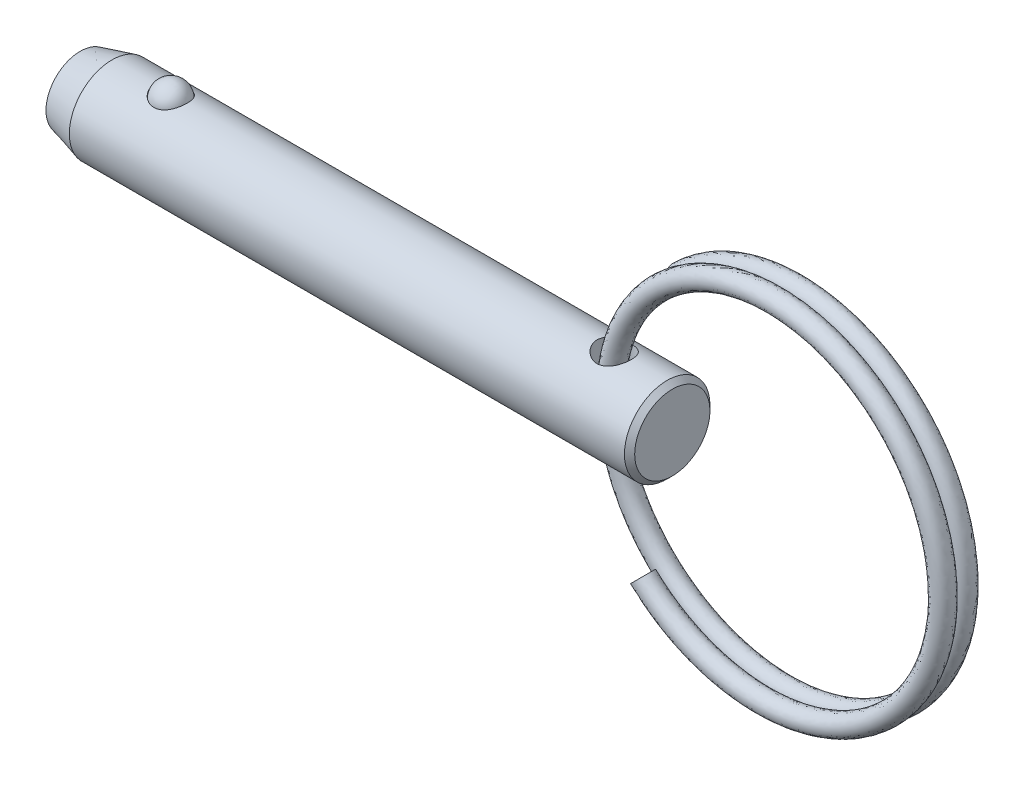
SolidWorks part; units mm, degrees
material "Plain Carbon Steel"
ref_plane "Front" through (0, 0, 0) normal (0, 0, 1) x (1, 0, 0)
ref_plane "Top" through (0, 0, 0) normal (0, 1, 0) x (1, 0, 0)
ref_plane "Right" through (0, 0, 0) normal (1, 0, 0) x (0, 0, -1)
sketch "Sketch1" plane through (0, 0, 0) normal (0, 0, 1) x (1, 0, 0)
  line L0 (21.9964, 2.794) -> (21.6154, 3.175)
  line L1 (21.6154, 3.175) -> (21.9964, 3.175) construction
  line L4 (21.9964, 2.794) -> (21.9964, 0)
  line L5 (21.9964, 3.175) -> (21.9964, 2.794) construction
  line L16 (21.6154, 3.175) -> (-19.6265, 3.175)
  line L17 (-21.9964, 3.175) -> (-21.9964, 2.54) construction
  line L19 (-19.6265, 3.175) -> (-21.9964, 3.175) construction
  line L22 (-21.9964, -3.175) -> (-19.6265, -3.175) construction
  line L23 (-15.2619, 2.8575) -> (-15.2619, -2.8575) construction
  line L24 (-21.9964, 0) -> (21.9964, 0)
  line L27 (21.9964, 0) -> (24.7904, 0) construction
  line L29 (-21.9964, 0) -> (-21.9964, -2.54) construction
  line L36 (16.4084, 0) -> (16.4084, 3.175) construction
  line L37 (-21.9964, 2.54) -> (-21.9964, 0)
  line L38 (-19.6265, -3.175) -> (21.9964, -3.175) construction
  line L39 (-21.9964, -2.54) -> (-21.9964, -3.175) construction
  line L40 (-19.6265, 3.175) -> (-21.9964, 2.54)
  line L42 (-19.6265, -3.175) -> (-21.9964, -2.54) construction
  line L43 (-19.6265, 3.175) -> (-19.6265, -3.175) construction
  circle A2 centre (-15.2619, 2.8575) radius 1.2319 construction
  point P35 (-14.0716, 3.175)
  dimension "A1" = 15
revolve "Revolve1" add sketch "Sketch1" angle 360 about L27
sketch "Sketch2" plane through (0, 0, 0) normal (0, 0, 1) x (1, 0, 0)
  line L0 (-14.0046, 2.8575) -> (-16.5192, 2.8575)
  line L1 (-15.2619, 4.0894) -> (-15.2619, 4.1148) construction
  line L2 (-14.0046, 2.8575) -> (-11.49, 2.8575) construction
  circle A0 centre (-15.2619, 2.8575) radius 1.2319 construction
  circle A1 centre (-15.2619, 2.8575) radius 1.2319 construction
  arc A2 (-16.5192, 2.8575) -> (-14.0046, 2.8575) centre (-15.2619, 2.8575) cw
  dimension "D1" = 0.0254
revolve "Cut-Revolve1" cut sketch "Sketch2" angle 360 about L2
sketch "Sketch3" plane through (0, 0, 0) normal (0, 0, 1) x (1, 0, 0)
  line L0 (-14.03, 2.8575) -> (-16.4938, 2.8575)
  line L1 (-14.03, 2.8575) -> (-11.5662, 2.8575) construction
  circle A0 centre (-15.2619, 2.8575) radius 1.2319 construction
  arc A1 (-14.03, 2.8575) -> (-16.4938, 2.8575) centre (-15.2619, 2.8575) ccw
revolve "Revolve2" add sketch "Sketch3" angle 360 about L1
sketch "Sketch4" plane through (0, 0, 0) normal (0, 0, 1) x (1, 0, 0)
  line L1 (17.6784, -3.175) -> (18.9484, -3.175)
  line L2 (17.6784, -3.175) -> (17.6784, 3.175)
  line L3 (17.6784, 3.175) -> (18.9484, 3.175)
  line L4 (18.9484, -3.175) -> (18.9484, 3.175)
  line L5 (17.6784, -3.175) -> (17.6784, -4.445) construction
  line L6 (18.9484, 3.175) -> (21.9964, 3.175) construction
  line L8 (16.4084, -3.175) -> (16.4084, 3.175) construction
  line L9 (16.4084, 0) -> (17.6784, 0) construction
  line L11 (17.6784, 0) -> (18.9484, 0) construction
  line L12 (21.6154, 3.175) -> (-19.6265, 3.175) construction
  line L14 (-19.6265, -3.175) -> (21.9964, -3.175) construction
  dimension "D1" = 2.54
revolve "Cut-Revolve2" cut sketch "Sketch4" angle 360 about L2
sketch "Sketch5" plane through (0, 0, 0) normal (0, 0, 1) x (1, 0, 0)
  line L0 (0, 0) -> (16.7014, 0) construction
  line L1 (16.7014, 0) -> (16.7014, 3.175) construction
  line L2 (21.6154, 3.175) -> (-19.6265, 3.175) construction
  line L3 (30.1634, 0) -> (43.6254, 0) construction
  line L4 (18.9484, 3.175) -> (18.6554, 3.175) construction
  line L5 (17.6784, 3.175) -> (18.9484, 3.175) construction
  line L6 (17.0812, 3.175) -> (17.0812, -3.175) construction
  line L7 (16.7014, 3.175) -> (16.4084, 3.175) construction
  line L8 (17.6784, -3.175) -> (18.9484, -3.175) construction
  line L9 (17.0812, -3.175) -> (18.9484, -3.175) construction
  line L10 (16.7014, 0) -> (30.1634, 0) construction
  line L12 (18.6554, 3.175) -> (17.0812, 3.175) construction
  line L13 (30.1634, 11.938) -> (30.1634, 13.462) construction
  circle A0 centre (30.1634, 0) radius 13.462
  circle A1 centre (30.1634, 0) radius 11.938 construction
  circle A2 centre (30.1634, 0) radius 12.7 construction
  point P26 (30.1634, 12.7)
curve "Helix/Spiral1" pitch 1.5494 height 1.3557 radius 13.462 left hand yes centre (30.1634, 0, 0) axis (0, 0, -1) start towards (1, 0, 0)
sketch "Sketch6" plane through (114.0038, 0, 0) normal (0, 1, 0) x (0, 0, -1)
  line L0 (0, 95.7784) -> (0, 96.5404) construction
  line L1 (0, 96.5404) -> (0, 97.3024) construction
  circle A0 centre (0, 96.5404) radius 0.762
  dimension "D1" = 1.524
sketch "Sketch7" plane through (0, 0, 0) normal (0, 0, 1) x (1, 0, 0)
  circle A0 centre (30.1634, 0) radius 13.462 construction
  circle A1 centre (30.1634, 0) radius 13.462
curve "Helix/Spiral2" pitch 1.5494 height 1.3557 radius 13.462 left hand yes centre (30.1634, 0, 0) axis (0, 0, 1) start towards (1, 0, 0)
sweep "Sweep1" add profiles "Sketch6" path "Helix/Spiral1"
sweep "Sweep2" add profiles "Sketch6<2>" path "Helix/Spiral2"
sketch "Sketch6<2>" plane through (114.0038, 0, 0) normal (0, 1, 0) x (0, 0, -1) same geometry as "Sketch6"
ref_plane "Top Mate Plane" through (16.4084, 0, 0) normal (1, 0, 0) x (0, 0, -1)
ref_plane "Bottom Mate Plane" through (-14.03, 0, 0) normal (1, 0, 0) x (0, 0, -1)
equation "\"D12@Sketch1\"=\"A@Sketch1\" * 0.80"
equation "\"D2@Sketch1\"=\"A@Sketch1\" * 0.9"
equation "\"D1@Sketch4\" = \"A@Sketch1\" / 2.5"
equation "\"Ring OD@Sketch5\" = \"R Ring Dia@Sketch5\" * 0.06"
equation "\"D4@Helix/Spiral1\"=\"Ring OD@Sketch5\" + 0.001"
equation "\"D1@Sketch6\"=\"Ring OD@Sketch5\""
equation "\"D4@Helix/Spiral2\" = \"D4@Helix/Spiral1\""
equation "\"D5@Helix/Spiral2\" = \"D5@Helix/Spiral1\""
